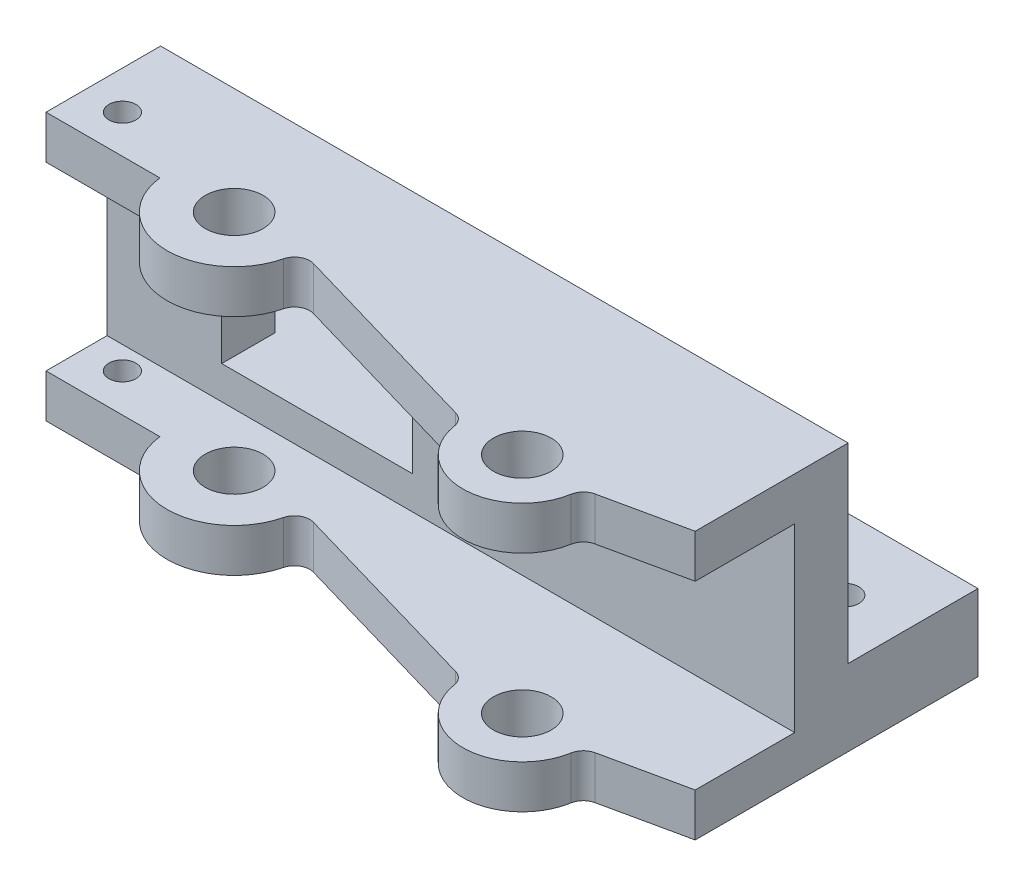
SolidWorks part; units mm, degrees
ref_plane "Front Plane" through (0, 0, 0) normal (0, 0, 1) x (1, 0, 0)
ref_plane "Top Plane" through (0, 0, 0) normal (0, 1, 0) x (1, 0, 0)
ref_plane "Right Plane" through (0, 0, 0) normal (1, 0, 0) x (0, 0, -1)
sketch "Sketch1" plane through (0, 0, 0) normal (0, 0, 1) x (1, 0, 0)
  line L1 (57.15, -22.225) -> (-57.15, -22.225)
  line L2 (57.15, -22.225) -> (57.15, 22.225)
  line L3 (57.15, 22.225) -> (-57.15, 22.225)
  line L4 (-57.15, -22.225) -> (-57.15, 22.225)
  line L5 (57.15, -22.225) -> (-57.15, 22.225) construction
  line L6 (57.15, 22.225) -> (-57.15, -22.225) construction
  point P0 (0, 0)
  dimension "D1" = 44.45
  dimension "D2" = 114.3
extrude "Boss-Extrude1" add sketch "Sketch1" along normal blind 62.23
sketch "Sketch2" plane through (0, 0, 62.23) normal (0, 0, 1) x (1, 0, 0)
  line L0 (-57.15, 22.225) -> (-57.15, -22.225) construction
  line L1 (57.15, -15.025) -> (-57.15, -15.025)
  line L2 (57.15, -15.025) -> (57.15, 15.025)
  line L3 (57.15, 15.025) -> (-57.15, 15.025)
  line L4 (-57.15, -15.025) -> (-57.15, 15.025)
  line L5 (57.15, -15.025) -> (-57.15, 15.025) construction
  line L6 (57.15, 15.025) -> (-57.15, -15.025) construction
  line L7 (57.15, 22.225) -> (-57.15, 22.225) construction
  point P0 (0, 0)
  dimension "D1" = 7.2
extrude "Cut-Extrude2" cut sketch "Sketch2" against normal blind 31.75
sketch "Sketch3" plane through (0, 0, 0) normal (0, 0, -1) x (-1, 0, 0)
  line L0 (-57.15, -22.225) -> (-57.15, 22.225) construction
  line L1 (57.15, 22.225) -> (-57.15, 22.225)
  line L2 (57.15, 22.225) -> (57.15, -9.525)
  line L3 (57.15, -9.525) -> (-57.15, -9.525)
  line L4 (-57.15, 22.225) -> (-57.15, -9.525)
  line L5 (57.15, -22.225) -> (-57.15, -22.225) construction
  dimension "D1" = 12.7
extrude "Cut-Extrude3" cut sketch "Sketch3" against normal blind 21.59
sketch "Sketch5" plane through (0, -22.225, 0) normal (0, -1, 0) x (1, 0, 0)
  line L0 (-3.81, 12.06) -> (46.99, 12.06) construction
  line L1 (57.15, 21.59) -> (-57.15, 21.59) construction
  line L2 (57.15, 62.23) -> (57.15, 0) construction
  circle A0 centre (-3.81, 12.06) radius 2.415
  circle A1 centre (46.99, 12.06) radius 2.415
  dimension "D3" = 4.83
  dimension "D4" = 10.16
  dimension "D1" = 9.53
  dimension "D2" = 50.8
extrude "Cut-Extrude4" cut sketch "Sketch5" against normal blind 25.4
sketch "Sketch7" plane through (0, -22.225, 0) normal (0, -1, 0) x (1, 0, 0)
  line L0 (57.15, 62.23) -> (57.15, 0) construction
  line L1 (-57.15, 0) -> (57.15, 0) construction
  circle A0 centre (31.75, 50.36) radius 4.8
  circle A1 centre (-27.14, 39.37) radius 4.8
  dimension "D1" = 9.6
  dimension "D2" = 25.4
  dimension "D3" = 39.37
  dimension "D4" = 9.6
  dimension "D5" = 58.89
  dimension "D6" = 10.99
extrude "Cut-Extrude6" cut sketch "Sketch7" against normal up to surface (44.45 mm away) up to face at (0, 22.225, 41.91)
sketch "Sketch9" plane through (0, 0, 30.48) normal (0, 0, 1) x (1, 0, 0)
  line L5 (57.15, 15.025) -> (-57.15, 15.025) construction
  line L6 (-38.1, 15.025) -> (-6.35, 15.025)
  line L7 (-38.1, 15.025) -> (-38.1, -15.025)
  line L8 (-38.1, -15.025) -> (-6.35, -15.025)
  line L9 (-6.35, 15.025) -> (-6.35, -15.025)
  line L10 (-57.15, -15.025) -> (57.15, -15.025) construction
  line L11 (-57.15, 15.025) -> (-57.15, -15.025) construction
  line L12 (57.15, -15.025) -> (57.15, 15.025) construction
  dimension "D1" = 63.5
  dimension "25in" = 19.05
extrude "Cut-Extrude7" cut sketch "Sketch9" against normal through all both and the other way through all
sketch "Sketch16" plane through (0, -22.225, 0) normal (0, -1, 0) x (1, 0, 0)
  line L1 (-38.1, 30.48) -> (-57.15, 30.48) construction
  line L4 (-38.2174, 40.64) -> (-38.2174, 30.48)
  line L8 (-57.15, 62.23) -> (57.15, 62.23)
  line L9 (57.15, 62.23) -> (57.15, 47.0103)
  line L10 (57.15, 62.23) -> (57.15, 0) construction
  line L11 (-15.99, 39.37) -> (21.87, 50.36)
  line L12 (41.63, 50.36) -> (57.15, 47.0103)
  line L13 (-49.091, 30.48) -> (-57.15, 30.48)
  line L14 (-38.2174, 30.48) -> (-49.091, 30.48)
  line L15 (-57.15, 30.48) -> (-57.15, 62.23)
  arc A2 (41.63, 50.36) -> (21.87, 50.36) centre (31.75, 50.36) ccw
  arc A3 (-15.99, 39.37) -> (-38.2174, 40.64) centre (-27.14, 39.37) ccw
  circle A4 centre (-27.14, 39.37) radius 4.8 construction
  circle A5 centre (31.75, 50.36) radius 4.8 construction
  dimension "D1" = 6.35
  dimension "D2" = 5.08
  dimension "D3" = 10.16
extrude "Cut-Extrude8" cut sketch "Sketch16" against normal through all
fillet "Fillet1" radius 2.54 6 edges at (21.87, 18.625, 50.36) (41.63, -18.625, 50.36) (41.63, 18.625, 50.36) (-15.99, 18.625, 39.37) (-15.99, -18.625, 39.37) (21.87, -18.625, 50.36)
sketch "Sketch14" plane through (-6.35, 0, 0) normal (-1, 0, 0) x (0, 0, 1)
  line L0 (0, -15.025) -> (30.48, -15.025) construction
  line L1 (21.59, -9.525) -> (0, -9.525)
  line L2 (21.59, -9.525) -> (21.59, -15.025)
  line L3 (21.59, -15.025) -> (0, -15.025)
  line L4 (0, -9.525) -> (0, -15.025)
extrude "Boss-Extrude2" add sketch "Sketch14" along normal up to next
sketch "Sketch17" plane through (0, 0, 21.59) normal (0, 0, 1) x (1, 0, 0)
  line L1 (-6.35, -15.025) -> (-38.1, -15.025)
  line L2 (-6.35, -15.025) -> (-6.35, -9.525)
  line L3 (-6.35, -9.525) -> (-38.1, -9.525)
  line L4 (-38.1, -15.025) -> (-38.1, -9.525)
extrude "Boss-Extrude3" add sketch "Sketch17" along normal up to surface (8.89 mm away) up to face at (25.4, 0, 30.48)
sketch "Sketch25" plane through (-38.2174, 0, 0) normal (-1, 0, 0) x (0, 0, 1)
  line L0 (40.64, 15.025) -> (30.48, 15.025) construction
  line L1 (30.48, 22.225) -> (40.64, 22.225)
  line L2 (30.48, 22.225) -> (30.48, 15.025)
  line L3 (30.48, 15.025) -> (40.64, 15.025)
  line L4 (40.64, 22.225) -> (40.64, 15.025)
  line L5 (39.37, -22.225) -> (50.52, -22.225) construction
  line L6 (30.48, -15.025) -> (40.64, -15.025)
  line L7 (30.48, -15.025) -> (30.48, -22.225)
  line L8 (30.48, -22.225) -> (40.64, -22.225)
  line L9 (40.64, -15.025) -> (40.64, -22.225)
  dimension "D1" = 10.16
extrude "Boss-Extrude5" add sketch "Sketch25" along normal up to surface (18.9326 mm away) up to face at (-57.15, -3.175, 17.3567)
sketch "Sketch28" plane through (0, -22.225, 0) normal (0, -1, 0) x (-1, 0, 0)
sketch "Sketch30" plane through (0, -22.225, 0) normal (0, -1, 0) x (-1, 0, 0)
  line L2 (57.15, -40.64) -> (38.2174, -40.64) construction
  line L4 (57.15, -40.64) -> (57.15, 0) construction
  point P10 (50.8, -34.29)
  point P19 (46.148, -33.4511)
  point P24 (68.6216, -54.3669)
  point P29 (89.2498, -67.4016)
  dimension "D1" = 6.35
  dimension "D2" = 6.35
hole_wizard "#8 Clearance Hole1" positions "Sketch30" profile "Sketch29" hole size "#8" standard "ANSI Inch" end condition through all
sketch "Sketch29" plane through (-50.8, -22.225, 34.29) normal (1, 0, 0) x (0, 0, -1)
  line L0 (0, 0) -> (0, 44.45)
  line L1 (0, 44.45) -> (2.2479, 44.45)
  line L2 (2.2479, 44.45) -> (2.2479, 0)
  line L5 (2.2479, 0) -> (0, 0)
  line L11 (0, -6.35) -> (0, 107.95) construction
  dimension "Thru Hole Dia." = 4.4958
  dimension "Thru Hole Depth" = 44.45
